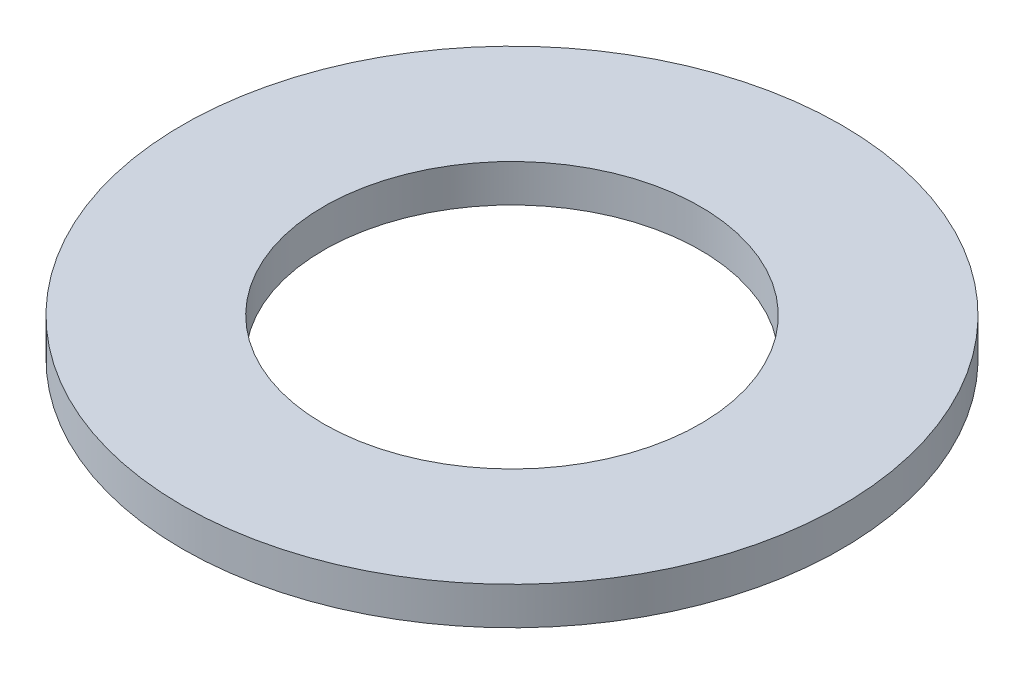
SolidWorks part; units mm, degrees
ref_plane "Front Plane" through (0, 0, 0) normal (0, 0, 1) x (1, 0, 0)
ref_plane "Top Plane" through (0, 0, 0) normal (0, 1, 0) x (1, 0, 0)
ref_plane "Right Plane" through (0, 0, 0) normal (1, 0, 0) x (0, 0, -1)
sketch "Sketch1" plane through (0, 0, 0) normal (0, 1, 0) x (1, 0, 0)
  circle A0 centre (0, 0) radius 52.5
  dimension "FLANGE_OD" = 105
extrude "Boss-Extrude1" add sketch "Sketch1" along normal blind 6
sketch "Sketch2" plane through (0, 0, 0) normal (0, 1, 0) x (1, 0, 0)
  circle A0 centre (0, 0) radius 30
  dimension "BORE_D" = 60
extrude "Cut-Extrude1" cut sketch "Sketch2" along normal through all
sketch "Sketch3" plane through (0, 6, 0) normal (0, 1, 0) x (1, 0, 0)
  circle A0 centre (0, 0) radius 20.3169 construction
  circle A1 centre (-20.3169, 0) radius 1.6565
  dimension "BOLT_D" = 3.3131
  dimension "BOLT_PCD" = 40.6338
extrude "Cut-Extrude2" cut sketch "Sketch3" against normal blind 5.9625 rebuild error yes
pattern_circular "CirPattern1" count 6 over 360 rebuild error yes
